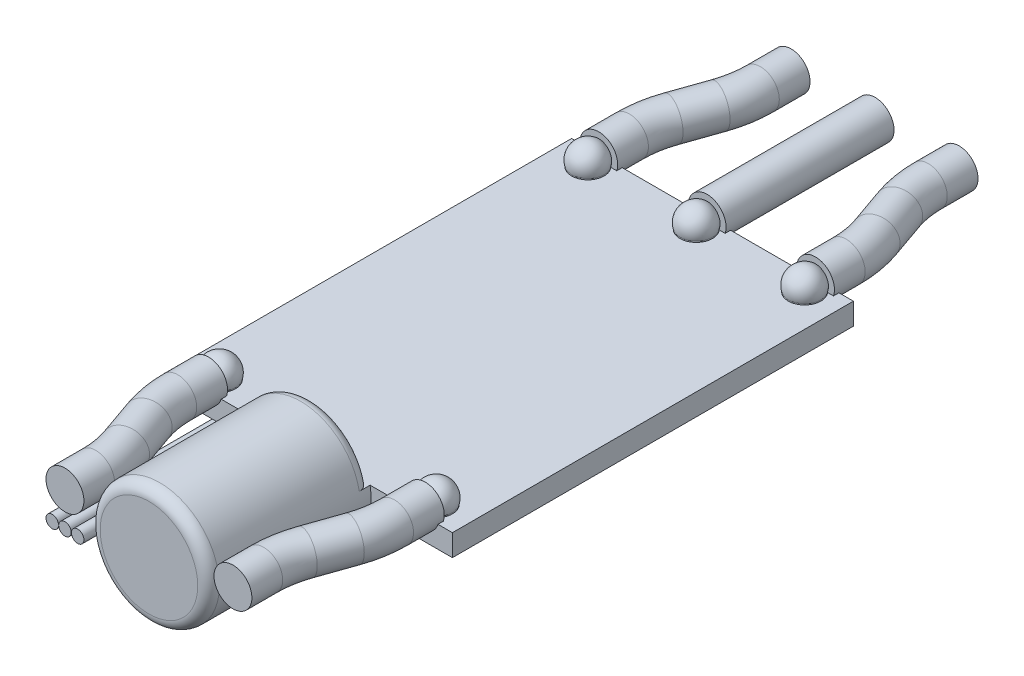
SolidWorks part; units mm, degrees
ref_plane "Front Plane" through (0, 0, 0) normal (0, 0, 1) x (1, 0, 0)
ref_plane "Top Plane" through (0, 0, 0) normal (0, 1, 0) x (1, 0, 0)
ref_plane "Right Plane" through (0, 0, 0) normal (1, 0, 0) x (0, 0, -1)
sketch "Sketch1" plane through (0, 0, 0) normal (0, 1, 0) x (1, 0, 0)
  line L1 (13, 18.5) -> (-13, 18.5)
  line L2 (13, 18.5) -> (13, -18.5)
  line L3 (13, -18.5) -> (-13, -18.5)
  line L4 (-13, 18.5) -> (-13, -18.5)
  line L5 (13, 18.5) -> (-13, -18.5) construction
  line L6 (13, -18.5) -> (-13, 18.5) construction
  point P0 (0, 0)
  dimension "D1" = 26
  dimension "D2" = 37
extrude "Boss-Extrude1" add sketch "Sketch1" along normal mid plane 2
sketch "Sketch2" plane through (0, 0, 18.5) normal (0, 0, 1) x (1, 0, 0)
  circle A0 centre (0, 0) radius 5.5
  dimension "D1" = 11
extrude "Boss-Extrude2" add sketch "Sketch2" along normal blind 15
sketch "Sketch4" plane through (0, 1, 0) normal (0, 1, 0) x (1, 0, 0)
  line L0 (5.4083, -18.5) -> (13, -18.5) construction
  line L1 (13, -18.5) -> (13, 18.5) construction
  line L2 (0, 0) -> (0, -18.5) construction
  line L3 (-5.4083, -18.5) -> (5.4083, -18.5) construction
  line L4 (0, 0) -> (13, 0) construction
  line L5 (0, 0) -> (0, 18.5) construction
  line L6 (13, 18.5) -> (-13, 18.5) construction
  circle A0 centre (10, -17) radius 1.5
  circle A1 centre (-10, -17) radius 1.5
  circle A2 centre (10, 17) radius 1.5
  circle A3 centre (-10, 17) radius 1.5
  circle A4 centre (0, 17) radius 1.5
  dimension "D1" = 3
  dimension "D2" = 3
extrude "Boss-Extrude3" add sketch "Sketch4" along normal blind 0.1
dome "Dome1" faces to dome 1 distance 2 reverse direction no elliptical dome no face at (10, 1.1, 18.5) parameters "D1"=2
dome "Dome2" faces to dome 1 distance 2 reverse direction no elliptical dome no face at (-10, 1.1, 15.5) parameters "D1"=2
dome "Dome3" faces to dome 1 distance 2 reverse direction no elliptical dome no face at (-10, 1.1, -15.5) parameters "D1"=2
dome "Dome4" faces to dome 1 distance 2 reverse direction no elliptical dome no face at (0, 1.1, -15.5) parameters "D1"=2
dome "Dome5" faces to dome 1 distance 2 reverse direction no elliptical dome no face at (10, 1.1, -18.5) parameters "D1"=2
ref_plane "Plane1" through (0, 0, 18) normal (0, 0, 1) x (1, 0, 0)
sketch "Sketch5" plane through (0, 0, 18) normal (0, 0, 1) x (1, 0, 0)
  line L1 (-13, 1) -> (-7, 1)
  line L2 (-13, 1) -> (-13, 5)
  line L3 (-13, 5) -> (-7, 5)
  line L4 (-7, 1) -> (-7, 5)
  line L5 (13, 1) -> (7, 1)
  line L6 (13, 1) -> (13, 5)
  line L7 (13, 5) -> (7, 5)
  line L8 (7, 1) -> (7, 5)
  dimension "D1" = 4
  dimension "D2" = 6
  dimension "D3" = 6
extrude "Cut-Extrude1" cut sketch "Sketch5" along normal through all
ref_plane "Plane2" through (0, 0, -18) normal (0, 0, -1) x (-1, 0, 0)
sketch "Sketch6" plane through (0, 0, -18) normal (0, 0, -1) x (-1, 0, 0)
  line L0 (13, 1) -> (13, -1) construction
  line L1 (-13, 1) -> (13, 1)
  line L2 (-13, 1) -> (-13, 5)
  line L3 (-13, 5) -> (13, 5)
  line L4 (13, 1) -> (13, 5)
  dimension "D1" = 4
extrude "Cut-Extrude2" cut sketch "Sketch6" along normal through all
ref_plane "Plane3" through (0, 0, 15.5) normal (0, 0, 1) x (1, 0, 0)
sketch "Sketch7" plane through (0, 0, 15.5) normal (0, 0, 1) x (1, 0, 0)
  line L0 (-8.925, -1.575) -> (-7.75, -1.575) construction
  line L1 (-7.75, -1.575) -> (-6.575, -1.575) construction
  line L2 (-13, -1) -> (-5.4083, -1) construction
  line L4 (-13, 1) -> (-13, -1) construction
  circle A0 centre (-6.575, -1.575) radius 0.575
  circle A1 centre (-7.75, -1.575) radius 0.575
  circle A2 centre (-8.925, -1.575) radius 0.575
  dimension "D1" = 1.15
  dimension "D2" = 3.5
  dimension "D3" = 3.5
extrude "Boss-Extrude4" add sketch "Sketch7" along normal up to surface (18 mm away) separate body up to face at (5.5, 0, 33.5)
sketch "Sketch8" plane through (0, 0, 18) normal (0, 0, 1) x (1, 0, 0)
  circle A0 centre (-10, 1.5375) radius 1.75
  circle A1 centre (10, 1.5375) radius 1.75 construction
  dimension "D1" = 3.5
  dimension "D2" = 3.5
sketch "Sketch9" plane through (0, 1, 0) normal (0, 1, 0) x (1, 0, 0)
  line L0 (-10, -18) -> (-10, -20.8378)
  line L1 (-11.75, -18) -> (-8.25, -18) construction
  line L2 (-9.4376, -24.1441) -> (-8.3124, -27.3559)
  line L3 (-7.75, -30.6622) -> (-7.75, -33.5)
  line L4 (-8.325, -33.5) -> (-7.175, -33.5) construction
  arc A0 (-9.4376, -24.1441) -> (-10, -20.8378) centre (0, -20.8378) cw
  arc A1 (-8.3124, -27.3559) -> (-7.75, -30.6622) centre (-17.75, -30.6622) cw
  dimension "D1" = 10
  dimension "D2" = 10
sweep "Sweep1" add profiles "Sketch8" path "Sketch9"
mirror "Mirror1" about plane through (0, 0, 0) normal (1, 0, 0) of "Sweep1"
mirror "Mirror2" about plane through (0, 0, 0) normal (0, 0, 1) of "Mirror1", "Sweep1"
sketch "Sketch11" plane through (0, 0, -18) normal (0, 0, -1) x (-1, 0, 0)
  circle A0 centre (0, 1.5375) radius 1.75
  dimension "D1" = 3.5
extrude "Boss-Extrude5" add sketch "Sketch11" along normal up to surface (15.5 mm away) up to face at (6, 1.5375, -33.5)
fillet "Fillet1" radius 1 3 edges at (0, 5.5, 18.5) (0, -5.5, 18.5) (5.5, 0, 33.5)
